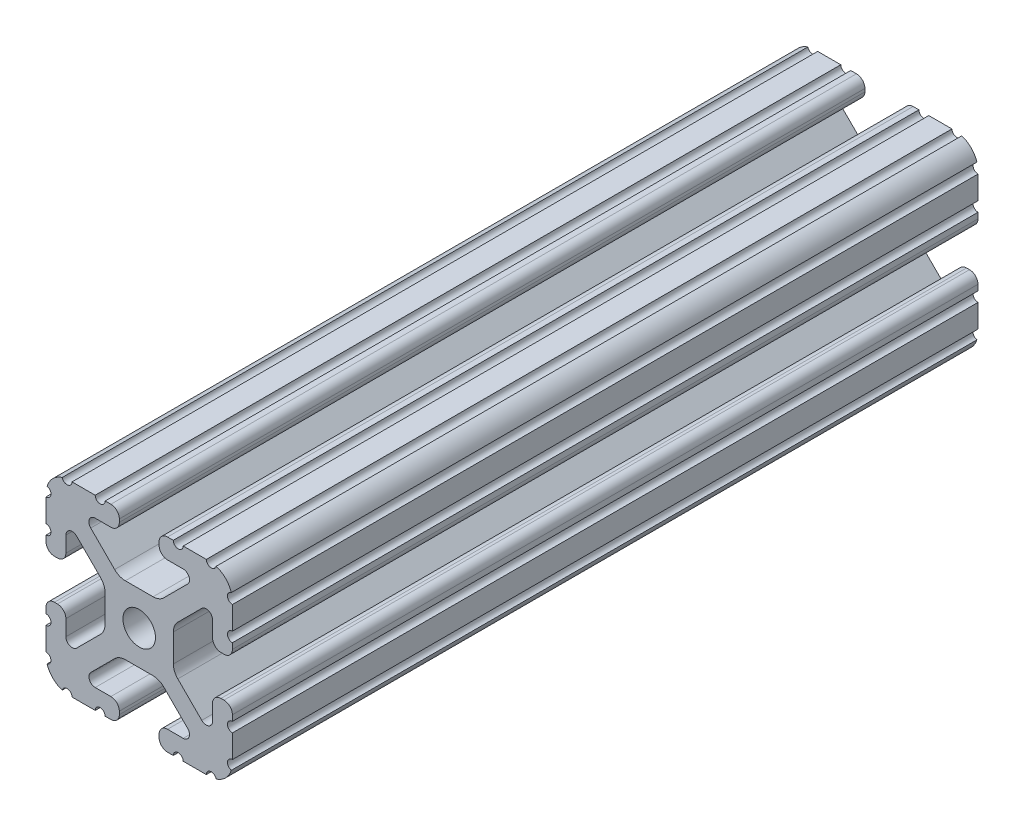
SolidWorks part; units mm, degrees
ref_plane "Front Plane" through (0, 0, 0) normal (0, 0, 1) x (1, 0, 0)
ref_plane "Top Plane" through (0, 0, 0) normal (0, 1, 0) x (1, 0, 0)
ref_plane "Right Plane" through (0, 0, 0) normal (1, 0, 0) x (0, 0, -1)
sketch "Sketch2" plane through (0, 0, 0) normal (0, 0, 1) x (1, 0, 0)
  line L0 (0, 19.05) -> (0, -19.05) construction
  line L1 (-19.05, 0) -> (19.05, 0) construction
  line L2 (4.064, -19.05) -> (19.05, -19.05)
  line L3 (19.05, -19.05) -> (19.05, -4.064)
  line L4 (4.064, -19.05) -> (4.064, -14.986)
  line L5 (4.064, -14.986) -> (12.1123, -14.986)
  line L6 (12.1123, -14.986) -> (4.1113, -6.985)
  line L7 (0, 0) -> (19.05, -19.05) construction
  line L8 (19.05, -4.064) -> (14.986, -4.064)
  line L9 (14.986, -4.064) -> (14.986, -12.1123)
  line L10 (14.986, -12.1123) -> (6.985, -4.1113)
  circle A0 centre (0, 0) radius 3.3274
  arc A1 (8.9963, -14.986) -> (9.909, -12.7826) centre (8.9963, -13.6953) ccw construction
  point P8 (0, -6.985)
  dimension "Center Hole Diameter" = 6.6548
  dimension "Rail Height" = 38.1
  dimension "Rail Width" = 38.1
  dimension "T-Slot Width" = 8.128
  dimension "Slot Inner Width" = 20.574
  dimension "Thickness" = 4.064
  dimension "Slot Depth" = 8.001
  dimension "D1" = 4.064
sketch "Sketch3" plane through (0, 0, 0) normal (1, 0, 0) x (0, 0, -1)
  line L0 (-76.2, -19.05) -> (76.2, -19.05) construction
  line L1 (-68.58, 0) -> (68.58, 0) construction
  dimension "Length" = 152.4
  dimension "D1" = 137.16
sketch "Sketch4" plane through (0, 0, 0) normal (0, 0, 1) x (1, 0, 0)
  line L0 (5.7912, -19.05) -> (14.3002, -19.05)
  line L1 (4.064, -19.05) -> (19.05, -19.05) construction
  line L2 (4.064, -19.05) -> (4.064, -14.986) construction
  line L3 (4.064, -14.986) -> (12.1123, -14.986) construction
  line L4 (4.064, -16.7132) -> (4.064, -17.3228)
  line L5 (5.7912, -14.986) -> (8.9963, -14.986)
  line L6 (0, -6.985) -> (2.833, -6.985)
  line L7 (12.1123, -14.986) -> (4.1113, -6.985) construction
  line L8 (5.0152, -7.8889) -> (9.909, -12.7826)
  line L9 (19.05, -19.05) -> (19.05, -4.064) construction
  line L10 (14.986, -12.1123) -> (6.985, -4.1113) construction
  line L11 (14.986, -4.064) -> (14.986, -12.1123) construction
  line L12 (14.986, -8.9963) -> (14.986, -5.7912)
  line L13 (19.05, -4.064) -> (14.986, -4.064) construction
  line L14 (16.7132, -4.064) -> (17.3228, -4.064)
  line L15 (19.05, -5.7912) -> (19.05, -14.3002)
  line L16 (12.7826, -9.909) -> (7.8889, -5.0152)
  line L17 (6.985, 0) -> (6.985, -2.833)
  line L18 (-19.05, 0) -> (19.05, 0) construction
  line L19 (0, -6.985) -> (0, -3.3274)
  line L20 (0, 19.05) -> (0, -19.05) construction
  line L21 (6.985, 0) -> (3.3274, 0)
  arc A0 (4.064, -17.3228) -> (5.7912, -19.05) centre (5.7912, -17.3228) ccw
  arc A2 (4.064, -16.7132) -> (5.7912, -14.986) centre (5.7912, -16.7132) cw
  arc A3 (8.9963, -14.986) -> (9.909, -12.7826) centre (8.9963, -13.6953) ccw
  arc A4 (2.833, -6.985) -> (5.0152, -7.8889) centre (2.833, -10.0711) cw
  arc A5 (14.3002, -19.05) -> (19.05, -14.3002) centre (14.3002, -14.3002) ccw
  arc A6 (12.7826, -9.909) -> (14.986, -8.9963) centre (13.6953, -8.9963) ccw
  arc A7 (14.986, -5.7912) -> (16.7132, -4.064) centre (16.7132, -5.7912) cw
  arc A8 (17.3228, -4.064) -> (19.05, -5.7912) centre (17.3228, -5.7912) cw
  arc A9 (7.8889, -5.0152) -> (6.985, -2.833) centre (10.0711, -2.833) cw
  circle A10 centre (0, 0) radius 3.3274 construction
  arc A11 (0, -3.3274) -> (3.3274, 0) centre (0, 0) ccw
  dimension "D1" = 4.7498
  dimension "D2" = 3.0861
  dimension "D3" = 1.7272
extrude "Boss-Extrude1" add sketch "Sketch4" along normal mid plane 152.4
sketch "Sketch5" plane through (0, 0, 0) normal (0, 0, 1) x (1, 0, 0)
  line L0 (4.064, -19.05) -> (19.05, -19.05) construction
  line L1 (5.7912, -14.986) -> (8.9963, -14.986) construction
  line L3 (0, 0) -> (19.05, -19.05) construction
  line L4 (8.9963, -14.986) -> (8.9963, -19.05) construction
  line L5 (12.1123, -14.986) -> (4.1113, -6.985) construction
  circle A0 centre (14.7395, -19.05) radius 1.016
  circle A1 centre (7.9803, -19.05) radius 1.016
  circle A2 centre (19.05, -14.7395) radius 1.016
  circle A3 centre (19.05, -7.9803) radius 1.016
  point P10 (7.3938, -14.986)
  point P12 (13.6953, -8.9963)
  dimension "D1" = 2.032
extrude "Cut-Extrude1" cut sketch "Sketch5" against normal through all both and the other way through all
mirror "Mirror1" about plane through (0, 0, 0) normal (1, 0, 0) of bodies 137 134
mirror "Mirror2" about plane through (0, 0, 0) normal (0, 1, 0) of bodies 135
ref_axis "Axis1" through (0, 0, 76.2) along (0, 0, -1)
ref_point "Point1"
equation "\"D1@Boss-Extrude1\"=\"Length@Sketch3\""
equation "\"D1@Sketch2\"=\"Thickness@Sketch2\""
equation "\"D2@Sketch4\"=\"Slot Inner Width@Sketch2\"*0.15"
equation "\"D1@Sketch4\"=\"D3@Sketch4\"*2.75"
equation "\"D3@Sketch4\"=\"Thickness@Sketch2\"*0.425"
equation "\"D1@Sketch5\"=\"Thickness@Sketch2\"*0.5"
equation "\"D1@Sketch3\"=\"Length@Sketch3\"*0.9"
